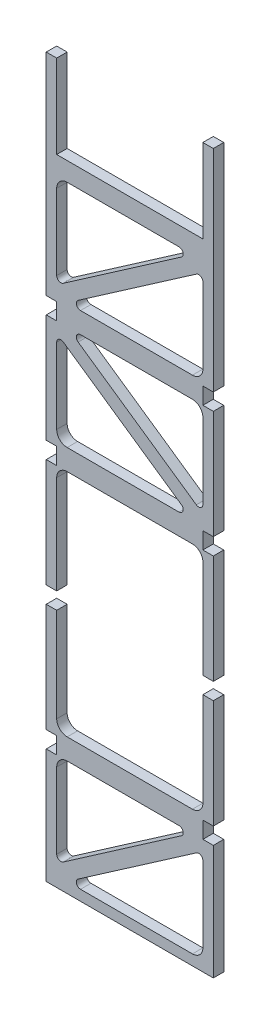
SolidWorks part; units mm, degrees
material "Balsa"
ref_plane "Front Plane" through (0, 0, 0) normal (0, 0, 1) x (1, 0, 0)
ref_plane "Top Plane" through (0, 0, 0) normal (0, 1, 0) x (1, 0, 0)
ref_plane "Right Plane" through (0, 0, 0) normal (1, 0, 0) x (0, 0, -1)
sketch "Model" plane through (0, 0, 0) normal (0, 0, 1) x (1, 0, 0)
  line L0 (-80.7688, 311.15) -> (-12.7, 311.15)
  line L1 (-10.3358, 365.5406) -> (-82.2146, 315.7784)
  line L2 (-6.35, 317.5) -> (-6.35, 363.4522)
  line L3 (-95.25, 287.2522) -> (-95.25, 241.3)
  line L4 (-19.3854, 239.5784) -> (-91.2642, 289.3406)
  line L5 (-88.9, 234.95) -> (-20.8312, 234.95)
  line L6 (-80.7688, 158.75) -> (-12.7, 158.75)
  line L7 (-10.3358, 213.1406) -> (-82.2146, 163.3784)
  line L8 (-6.35, 165.1) -> (-6.35, 211.0522)
  line L9 (-20.8312, 222.25) -> (-88.9, 222.25)
  line L10 (-91.2642, 167.8594) -> (-19.3854, 217.6216)
  line L11 (-95.25, 215.9) -> (-95.25, 169.9478)
  line L12 (-82.2146, 293.8216) -> (-10.3358, 244.0594)
  line L13 (-12.7, 298.45) -> (-80.7688, 298.45)
  line L14 (-6.35, 246.1478) -> (-6.35, 292.1)
  line L15 (-95.25, 134.8522) -> (-95.25, 88.9)
  line L16 (-19.3854, 87.1784) -> (-91.2642, 136.9406)
  line L17 (-88.9, 82.55) -> (-20.8312, 82.55)
  line L18 (-80.7688, 6.35) -> (-12.7, 6.35)
  line L19 (-10.3358, 60.7406) -> (-82.2146, 10.9784)
  line L20 (-6.35, 12.7) -> (-6.35, 58.6522)
  line L21 (-20.8312, 69.85) -> (-88.9, 69.85)
  line L22 (-91.2642, 15.4594) -> (-19.3854, 65.2216)
  line L23 (-95.25, 63.5) -> (-95.25, 17.5478)
  line L24 (-20.8312, 374.65) -> (-88.9, 374.65)
  line L25 (-91.2642, 320.2594) -> (-19.3854, 370.0216)
  line L26 (-95.25, 368.3) -> (-95.25, 322.3478)
  line L27 (-82.2146, 141.4216) -> (-10.3358, 91.6594)
  line L28 (-12.7, 146.05) -> (-80.7688, 146.05)
  line L29 (-6.35, 93.7478) -> (-6.35, 139.7)
  line L30 (-95.25, 386.08) -> (-6.35, 386.08)
  line L31 (-95.25, 386.08) -> (-95.25, 436.88)
  line L32 (-101.6, 436.88) -> (-95.25, 436.88)
  line L33 (-101.6, 0) -> (-101.6, 436.88)
  line L34 (-101.6, 0) -> (0, 0)
  line L35 (0, 0) -> (0, 436.88)
  line L36 (-6.35, 436.88) -> (0, 436.88)
  line L37 (-6.35, 386.08) -> (-6.35, 436.88)
  arc A0 (-12.7, 311.15) -> (-6.35, 317.5) centre (-12.7, 317.5) ccw
  arc A1 (-82.2146, 315.7784) -> (-80.7688, 311.15) centre (-80.7688, 313.69) ccw
  arc A2 (-6.35, 363.4522) -> (-10.3358, 365.5406) centre (-8.89, 363.4522) ccw
  arc A3 (-95.25, 241.3) -> (-88.9, 234.95) centre (-88.9, 241.3) ccw
  arc A4 (-91.2642, 289.3406) -> (-95.25, 287.2522) centre (-92.71, 287.2522) ccw
  arc A5 (-20.8312, 234.95) -> (-19.3854, 239.5784) centre (-20.8312, 237.49) ccw
  arc A6 (-12.7, 158.75) -> (-6.35, 165.1) centre (-12.7, 165.1) ccw
  arc A7 (-82.2146, 163.3784) -> (-80.7688, 158.75) centre (-80.7688, 161.29) ccw
  arc A8 (-6.35, 211.0522) -> (-10.3358, 213.1406) centre (-8.89, 211.0522) ccw
  arc A9 (-88.9, 222.25) -> (-95.25, 215.9) centre (-88.9, 215.9) ccw
  arc A10 (-19.3854, 217.6216) -> (-20.8312, 222.25) centre (-20.8312, 219.71) ccw
  arc A11 (-95.25, 169.9478) -> (-91.2642, 167.8594) centre (-92.71, 169.9478) ccw
  arc A12 (-10.3358, 244.0594) -> (-6.35, 246.1478) centre (-8.89, 246.1478) ccw
  arc A13 (-80.7688, 298.45) -> (-82.2146, 293.8216) centre (-80.7688, 295.91) ccw
  arc A14 (-6.35, 292.1) -> (-12.7, 298.45) centre (-12.7, 292.1) ccw
  arc A15 (-95.25, 88.9) -> (-88.9, 82.55) centre (-88.9, 88.9) ccw
  arc A16 (-91.2642, 136.9406) -> (-95.25, 134.8522) centre (-92.71, 134.8522) ccw
  arc A17 (-20.8312, 82.55) -> (-19.3854, 87.1784) centre (-20.8312, 85.09) ccw
  arc A18 (-12.7, 6.35) -> (-6.35, 12.7) centre (-12.7, 12.7) ccw
  arc A19 (-82.2146, 10.9784) -> (-80.7688, 6.35) centre (-80.7688, 8.89) ccw
  arc A20 (-6.35, 58.6522) -> (-10.3358, 60.7406) centre (-8.89, 58.6522) ccw
  arc A21 (-88.9, 69.85) -> (-95.25, 63.5) centre (-88.9, 63.5) ccw
  arc A22 (-19.3854, 65.2216) -> (-20.8312, 69.85) centre (-20.8312, 67.31) ccw
  arc A23 (-95.25, 17.5478) -> (-91.2642, 15.4594) centre (-92.71, 17.5478) ccw
  arc A24 (-88.9, 374.65) -> (-95.25, 368.3) centre (-88.9, 368.3) ccw
  arc A25 (-19.3854, 370.0216) -> (-20.8312, 374.65) centre (-20.8312, 372.11) ccw
  arc A26 (-95.25, 322.3478) -> (-91.2642, 320.2594) centre (-92.71, 322.3478) ccw
  arc A27 (-10.3358, 91.6594) -> (-6.35, 93.7478) centre (-8.89, 93.7478) ccw
  arc A28 (-80.7688, 146.05) -> (-82.2146, 141.4216) centre (-80.7688, 143.51) ccw
  arc A29 (-6.35, 139.7) -> (-12.7, 146.05) centre (-12.7, 139.7) ccw
extrude "Boss-Extrude1" add sketch "Model" along normal blind 6.35
sketch "Sketch1" plane through (0, 0, 6.35) normal (0, 0, 1) x (1, 0, 0)
  line L0 (-95.25, 215.9) -> (-95.25, 169.9478) construction
  line L1 (-12.7, 82.55) -> (-88.9, 82.55)
  line L2 (-6.35, 88.9) -> (-6.35, 215.9)
  line L3 (-12.7, 222.25) -> (-88.9, 222.25)
  line L4 (-95.25, 88.9) -> (-95.25, 215.9)
  line L5 (-20.8312, 222.25) -> (-88.9, 222.25) construction
  line L6 (-88.9, 82.55) -> (-20.8312, 82.55) construction
  arc A0 (-88.9, 82.55) -> (-95.25, 88.9) centre (-88.9, 88.9) cw
  arc A1 (-88.9, 222.25) -> (-95.25, 215.9) centre (-88.9, 215.9) ccw
  arc A2 (-6.35, 215.9) -> (-12.7, 222.25) centre (-12.7, 215.9) ccw
  arc A3 (-12.7, 82.55) -> (-6.35, 88.9) centre (-12.7, 88.9) ccw
  point P14 (-95.25, 222.25)
  point P17 (-6.35, 222.25)
  dimension "D2" = 6.35
  dimension "D1" = 88.9
extrude "Cut-Extrude1" cut sketch "Sketch1" against normal up to surface (6.35 mm away) up to face at (-50.8, 314.96, 0)
sketch "Sketch2" plane through (0, 0, 6.35) normal (0, 0, 1) x (1, 0, 0)
  line L0 (-101.6, 298.45) -> (0, 298.45)
  line L1 (-95.25, 63.5) -> (-95.25, 17.5478) construction
  line L2 (-101.6, 436.88) -> (-101.6, 0) construction
  line L3 (0, 0) -> (0, 436.88) construction
  line L4 (-101.6, 222.25) -> (0, 222.25)
  line L5 (-101.6, 80.01) -> (-95.25, 80.01)
  line L6 (-12.7, 298.45) -> (-80.7688, 298.45) construction
  line L7 (-101.6, 308.61) -> (-95.25, 308.61)
  line L8 (-101.6, 308.61) -> (-101.6, 298.45)
  line L9 (-101.6, 298.45) -> (-95.25, 298.45)
  line L10 (-95.25, 308.61) -> (-95.25, 298.45)
  line L11 (-101.6, 232.41) -> (-95.25, 232.41)
  line L12 (-101.6, 232.41) -> (-101.6, 222.25)
  line L13 (-101.6, 222.25) -> (-95.25, 222.25)
  line L14 (-95.25, 232.41) -> (-95.25, 222.25)
  line L15 (-12.7, 222.25) -> (-88.9, 222.25) construction
  line L16 (-95.25, 215.9) -> (-95.25, 88.9) construction
  line L17 (-101.6, 156.21) -> (-95.25, 156.21)
  line L18 (-101.6, 156.21) -> (-101.6, 146.05)
  line L19 (-101.6, 146.05) -> (-95.25, 146.05)
  line L20 (-95.25, 156.21) -> (-95.25, 146.05)
  line L21 (-101.6, 80.01) -> (-101.6, 69.85)
  line L22 (-101.6, 69.85) -> (-95.25, 69.85)
  line L23 (-95.25, 80.01) -> (-95.25, 69.85)
  line L24 (-50.8, 0) -> (-50.8, 386.08) construction
  line L25 (-101.6, 0) -> (0, 0) construction
  line L26 (-6.35, 386.08) -> (-95.25, 386.08) construction
  line L27 (0, 69.85) -> (-6.35, 69.85)
  line L28 (-6.35, 80.01) -> (-6.35, 69.85)
  line L29 (0, 80.01) -> (-6.35, 80.01)
  line L30 (0, 80.01) -> (0, 69.85)
  line L31 (0, 146.05) -> (-6.35, 146.05)
  line L32 (-6.35, 156.21) -> (-6.35, 146.05)
  line L33 (0, 156.21) -> (-6.35, 156.21)
  line L34 (0, 156.21) -> (0, 146.05)
  line L35 (0, 222.25) -> (-6.35, 222.25)
  line L36 (-6.35, 232.41) -> (-6.35, 222.25)
  line L37 (0, 232.41) -> (-6.35, 232.41)
  line L38 (0, 232.41) -> (0, 222.25)
  line L39 (0, 298.45) -> (-6.35, 298.45)
  line L40 (-6.35, 308.61) -> (-6.35, 298.45)
  line L41 (0, 308.61) -> (-6.35, 308.61)
  line L42 (0, 308.61) -> (0, 298.45)
  dimension "D1" = 6.35
  dimension "D2" = 10.16
  dimension "D3" = 10.16
  dimension "D4" = 66.04
  dimension "D5" = 10.16
  dimension "D6" = 10.16
  dimension "D7" = 66.04
extrude "Cut-Extrude2" cut sketch "Sketch2" against normal up to surface (6.35 mm away) contours L14 L11 L12 L4 | L10 L7 L8 L0 | L30 L29 L28 L27 | L34 L33 L32 L31 | L42 L41 L40 L0 | L38 L37 L36 L4 | L18 L17 L20 L19 | L21 L5 L23 L22 region at (-98.425, 303.53, 6.35) region at (-3.175, 303.53, 6.35) region at (-98.425, 227.33, 6.35) region at (-3.175, 227.33, 6.35) region at (-3.175, 74.93, 6.35) region at (-3.175, 151.13, 6.35) up to face at (-50.8, 152.4, 0)
equation "\"thick\"=0.25"
equation "\"D1@Boss-Extrude1\"=\"thick\""
